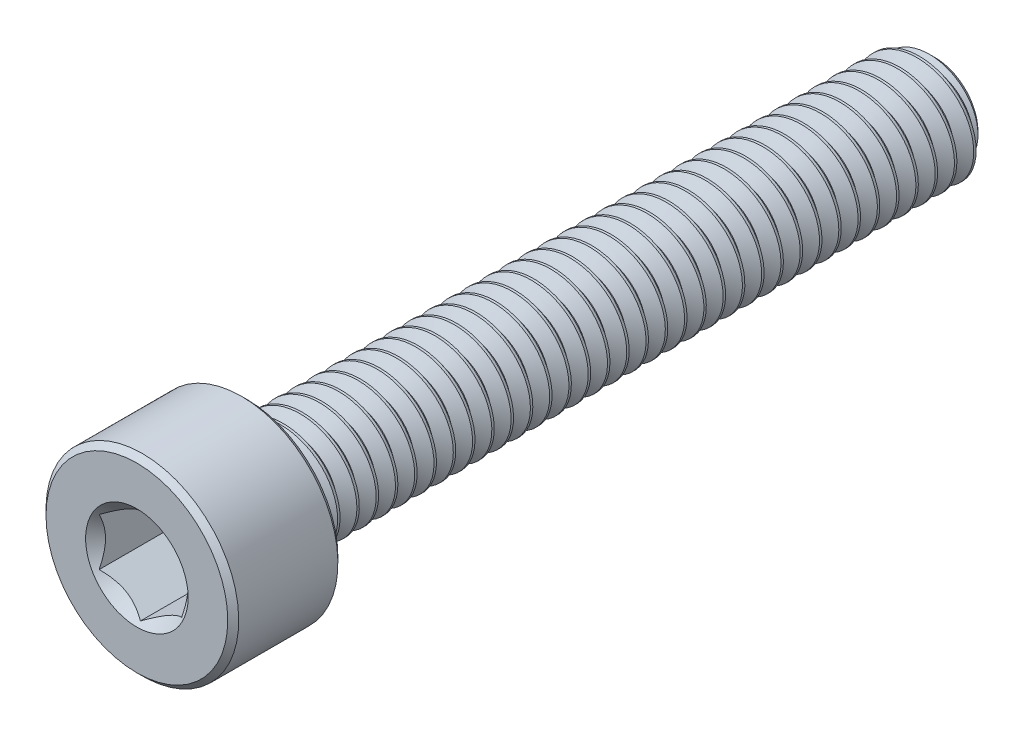
SolidWorks part; units mm, degrees
ref_plane "Front Plane" through (0, 0, 0) normal (0, 0, 1) x (1, 0, 0)
ref_plane "Top Plane" through (0, 0, 0) normal (0, 1, 0) x (1, 0, 0)
ref_plane "Right Plane" through (0, 0, 0) normal (1, 0, 0) x (0, 0, -1)
sketch "Sketch1" plane through (0, 0, 0) normal (1, 0, 0) x (0, 0, -1)
  line L0 (-14.5, 0) -> (14.5, 0) construction
  line L1 (14.5, 0) -> (14.5, 1.5453) construction
  line L2 (14.5, 1.5453) -> (14.0453, 2) construction
  line L3 (14.0453, 2) -> (13.975, 2) construction
  line L4 (13.975, 2) -> (-10.5, 2) construction
  line L5 (-10.5, 2) -> (-10.5, 3.5) construction
  line L6 (-10.5, 3.5) -> (-14.5, 3.5) construction
  line L7 (-14.5, 3.5) -> (-14.5, 0) construction
  line L8 (14.5, 1.5453) -> (14.5, 2) construction
  line L9 (14.4563, 2.0758) -> (14.8063, 1.4696) construction
  line L10 (14.8063, 1.4696) -> (15.1563, 2.0758) construction
  line L11 (15.1563, 2.0758) -> (14.4563, 2.0758) construction
  line L12 (14.8063, 2.0758) -> (14.8063, 2) construction
  line L13 (14.8063, 1.4696) -> (14.8063, 1.5453) construction
  line L14 (14.7625, 1.5453) -> (14.85, 1.5453) construction
  line L15 (14.5, 2) -> (15.1125, 2) construction
  line L16 (14.4781, 2.0379) -> (15.1344, 2.0379) construction
  line L17 (14.5, 0) -> (14.5, -2) construction
  line L18 (-10.7, 3.5) -> (-10.5, 3.3) construction
  line L19 (-14.3, 3.5) -> (-14.5, 3.3) construction
  line L20 (-10.5, 2) -> (-10.5, 0) construction
  line L21 (-10.5, 1) -> (-2.1667, 1) construction
  line L22 (-2.1667, 1) -> (6.1667, 1) construction
  line L23 (6.1667, 1) -> (14.5, 1) construction
  line L24 (-2.1667, 1) -> (-2.1667, 2) construction
  line L25 (-2.1667, 2) -> (-2.1667, 3.5) construction
  line L26 (6.1667, 1) -> (6.1667, 3.5) construction
  point P0 (-14.5, 1.5)
  point P3 (12.75, 2)
  point P4 (0, 0)
  point P18 (6.1667, 2)
  point P22 (14.8063, 1.5453)
  point P24 (13.975, 2)
  point P25 (14.8063, 2)
  point P28 (14.8063, 2.0379)
  point P29 (12.75, -2)
  point P30 (-2.1667, 2)
  point P31 (-12.5, 3.5)
  point P37 (-11.2, 3.5)
  point P38 (-14.2, 3.5)
  point P45 (-2.1667, 1)
  point P46 (6.1667, 1)
  dimension "D2" = 0.0875
  dimension "D7" = 0.2
  dimension "D8" = 0.2
  dimension "D9" = 0.2
  dimension "D10" = 0.1
  dimension "D11" = 0.5
  dimension "Drive Size" = 3
  dimension "Head Diameter" = 7
  dimension "Head Height" = 4
  dimension "Thread Pitch" = 0.7
  dimension "Thread Size" = 4
  dimension "Length" = 25
  dimension "D12" = 0.525
  dimension "D4" = 1.75
  dimension "D3" = 45
sketch "Sketch2" plane through (0, 0, 0) normal (1, 0, 0) x (0, 0, -1)
  line L0 (-14.5, 0) -> (-14.5, 3.3)
  line L1 (-14.3, 3.5) -> (-10.7, 3.5)
  line L2 (-10.5, 3.3) -> (-10.5, 2.2)
  line L4 (14.0453, 2) -> (14.5, 1.5453)
  line L5 (14.5, 1.5453) -> (14.5, 0)
  line L6 (-10.5, 3.5) -> (-14.5, 3.5) construction
  line L7 (14.5, 0) -> (-14.5, 0)
  line L8 (-14.3, 3.5) -> (-14.5, 3.3) construction
  line L10 (-14.3, 3.5) -> (-14.5, 3.3)
  line L14 (-10.7, 3.5) -> (-10.5, 3.3) construction
  line L16 (-10.7, 3.5) -> (-10.5, 3.3)
  line L17 (-10.5, 2) -> (-10.5, 3.5) construction
  line L19 (-10.3, 2) -> (14.0453, 2)
  line L20 (13.975, 2) -> (-10.5, 2) construction
  arc A1 (-10.5, 2.2) -> (-10.3, 2) centre (-10.3, 2.2) ccw
  dimension "D3" = 0.2
revolve "Revolve1" add sketch "Sketch2" angle 360 about L7
sketch "Sketch3" plane through (0, 0, 14.5) normal (0, 0, 1) x (1, 0, 0)
  line L1 (1.5, -0.866) -> (1.5, 0.866)
  line L2 (1.5, 0.866) -> (0, 1.7321)
  line L3 (0, 1.7321) -> (-1.5, 0.866)
  line L4 (-1.5, 0.866) -> (-1.5, -0.866)
  line L5 (-1.5, -0.866) -> (0, -1.7321)
  line L6 (0, -1.7321) -> (1.5, -0.866)
  circle A0 centre (0, 0) radius 1.5 construction
  circle A1 centre (0, 0) radius 3.5 construction
  circle A2 centre (0, 0) radius 3.5 construction
  circle A3 centre (0, 0) radius 1.7321 construction
  point P13 (0, 0)
  dimension "D1" = 3.4641
extrude "Cut-Extrude1" cut sketch "Sketch3" against normal offset from surface (3 mm away) 1 up to face at (0, 3.3, 10.5)
sketch "Sketch4" plane through (0, 0, 14.5) normal (0, 0, 1) x (1, 0, 0)
  circle A0 centre (0, 0) radius 1.862
  dimension "D1" = 3.7239
extrude "Cut-Extrude2" cut sketch "Sketch4" against normal up to vertex (2 mm away) draft 45 up to point (0, 3.5, 12.5)
sketch "Sketch11" plane through (0, 0, 0) normal (1, 0, 0) x (0, 0, -1)
  line L0 (-14.5, 0) -> (14.5, 0) construction
  line L1 (-14.5, 0) -> (14.5, 0) construction
  line L2 (-5.8125, 0) -> (-5.8125, 2) construction
  line L3 (13.975, 2) -> (-10.5, 2) construction
  line L4 (9.8125, 0) -> (9.8125, 2) construction
  line L6 (14.5, 1.5453) -> (14.5, 2) construction
  point P2 (-5.8125, 0)
  point P3 (9.8125, 0)
  dimension "D1" = 4.6875
  dimension "D2" = 4.6875
sketch "Sketch6" plane through (0, 0, -14.5) normal (0, 0, -1) x (-1, 0, 0)
  circle A0 centre (0, 0) radius 2
curve "Helix/Spiral1" pitch 0.7 height 25.7 turns 36.7143
sketch "Sketch10" plane through (0, 0, 0) normal (1, 0, 0) x (0, 0, -1)
  line L0 (-10.3, -3.5) -> (-10.3, 3.5)
  line L5 (-14.5, 0) -> (14.5, 0) construction
  line L6 (-10.3, 2) -> (-10.3, -2) construction
  point P3 (-10.3, 0)
split "Split1" trim tools "Sketch10" bodies to split 106 resulting bodies 114 115
sketch "Sketch7" plane through (0, 0, 0) normal (1, 0, 0) x (0, 0, -1)
  line L0 (14.4781, 2.0379) -> (15.1344, 2.0379)
  line L1 (15.1344, 2.0379) -> (14.85, 1.5453)
  line L2 (14.85, 1.5453) -> (14.7625, 1.5453)
  line L3 (14.7625, 1.5453) -> (14.4781, 2.0379)
sweep "Cut-Sweep1" cut profiles "Sketch7" path "Helix/Spiral1"
sketch "Sketch8" plane through (0, 0, 0) normal (1, 0, 0) x (0, 0, -1)
  line L0 (-10.5, 0) -> (-10.5, 2)
  line L1 (-10.3, -2) -> (-10.3, 2) construction
  line L2 (-10.5, 2) -> (-10.3, 2)
  line L4 (-10.3, 2) -> (-9.1453, 0)
  line L5 (-9.1453, 0) -> (-10.5, 0)
  line L6 (13.975, 2) -> (-10.5, 2) construction
  line L7 (-14.5, 0) -> (14.5, 0) construction
  dimension "D1" = 60
revolve "Revolve2" add sketch "Sketch8" angle 360 about L5
equation "\"D2@Sketch1\" = \"Thread Pitch@Sketch1\" / 8"
equation "\"D4@Helix/Spiral1\" = \"Thread Pitch@Sketch1\""
equation "\"D7@Sketch1\" = \"Head Height@Sketch1\" * .05"
equation "\"D8@Sketch1\"=\"D7@Sketch1\""
equation "\"D9@Sketch1\"=\"D7@Sketch1\""
equation "\"D10@Sketch1\"=\"D7@Sketch1\"/2"
equation "\"D11@Sketch1\"=\"D10@Sketch1\"*5"
equation "\"D4@Sketch1\"=\"Thread Pitch@Sketch1\"*2.5"
equation "\"D12@Sketch1\"=\"Thread Pitch@Sketch1\"*.75"
equation "\"D3@Helix/Spiral1\"=\"Length@Sketch1\"+\"Thread Pitch@Sketch1\""
equation "\"D3@Sketch2\"=\"Thread Size@Sketch1\"*0.05"
equation "\"D1@Sketch11\"=\"Length@Sketch1\"*0.1875"
equation "\"D2@Sketch11\"=\"D1@Sketch11\""
equation "\"D1@Sketch4\"=\"D1@Sketch3\"*1.075"
